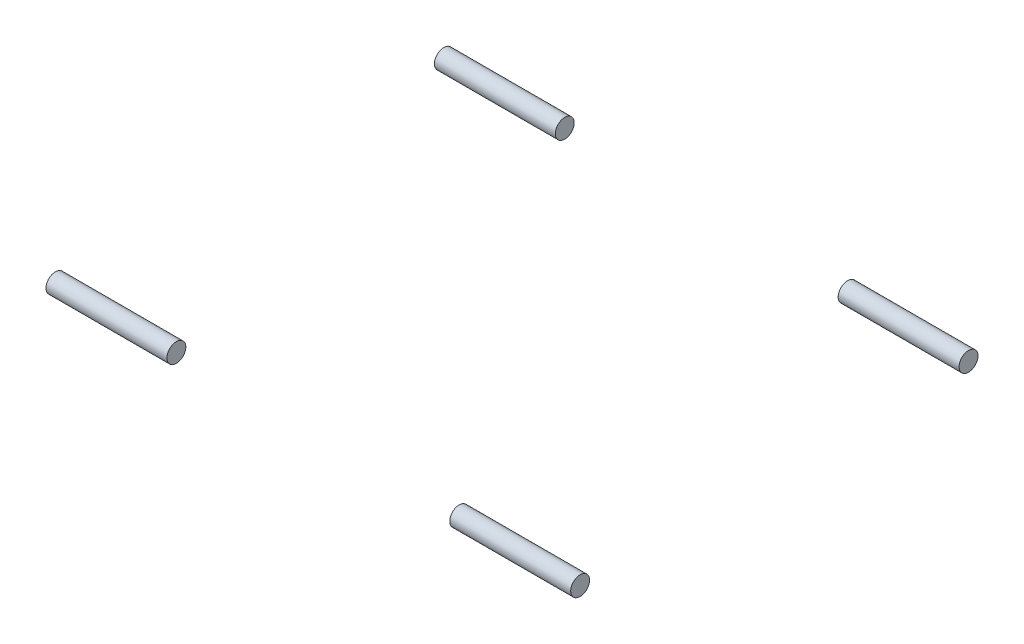
SolidWorks part; units mm, degrees
material "6061-T6 (SS)"
ref_plane "Front Plane" through (0, 0, 0) normal (0, 0, 1) x (1, 0, 0)
ref_plane "Top Plane" through (0, 0, 0) normal (0, 1, 0) x (1, 0, 0)
ref_plane "Right Plane" through (0, 0, 0) normal (1, 0, 0) x (0, 0, -1)
sketch "Sketch1" plane through (88.15, 0, 0) normal (-1, 0, 0) x (0, 0, 1)
  circle A0 centre (130.5, 0) radius 3.175
  circle A1 centre (0, 0) radius 3.175
  circle A2 centre (0, 0) radius 3.175 construction
  circle A3 centre (130.5, 0) radius 3.175 construction
extrude "Boss-Extrude1" add sketch "Sketch1" along normal up to surface (40.64 mm away)
mirror "Mirror1" about plane through (0, 0, 0) normal (1, 0, 0) of bodies 101 102
